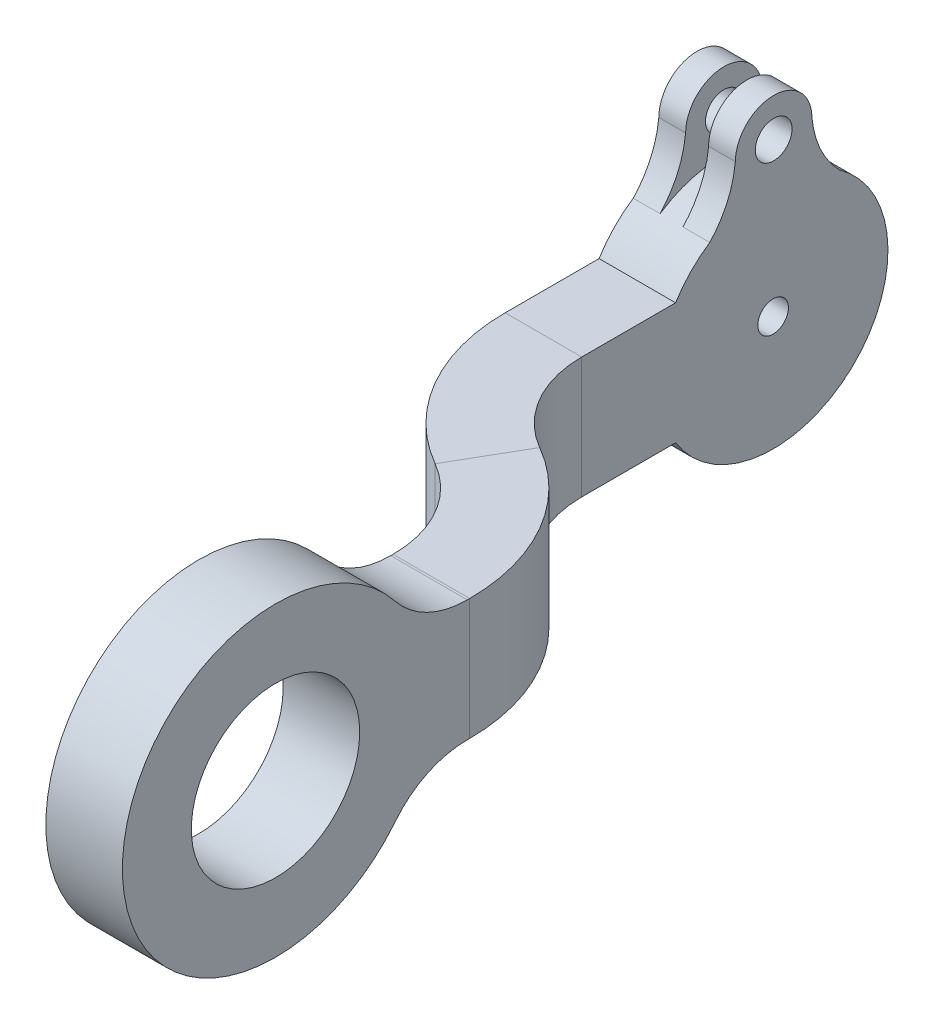
SolidWorks part; units mm, degrees
material "Resina de melamina"
ref_plane "Alzado" through (0, 0, 0) normal (0, 0, 1) x (1, 0, 0)
ref_plane "Planta" through (0, 0, 0) normal (0, 1, 0) x (1, 0, 0)
ref_plane "Vista lateral" through (0, 0, 0) normal (1, 0, 0) x (0, 0, -1)
sketch "Croquis1" plane through (0, 0, 0) normal (0, 1, 0) x (1, 0, 0)
  line L0 (0, 0) -> (0, 60) construction
  line L1 (0, 60) -> (-20, 60) construction
  line L2 (-20, 60) -> (-20, 85) construction
  line L3 (0, 15) -> (-20, 25.359) construction
  line L4 (-20, 85) -> (-20, 60)
  line L5 (0, 25.359) -> (0, 0)
  arc A0 (-20, 60) -> (-10, 42.6795) centre (0, 60) ccw
  arc A1 (0, 25.359) -> (-10, 42.6795) centre (-20, 25.359) ccw
  dimension "D4" = 20
  dimension "D1" = 60
  dimension "D2" = 25
  dimension "D3" = 20
sketch "Croquis2" plane through (0, 0, 0) normal (0, 0, 1) x (1, 0, 0)
  line L1 (5, -7.9175) -> (-5, -7.9175)
  line L2 (5, -7.9175) -> (5, 7.9175)
  line L3 (5, 7.9175) -> (-5, 7.9175)
  line L4 (-5, -7.9175) -> (-5, 7.9175)
  line L5 (5, -7.9175) -> (-5, 7.9175) construction
  line L6 (5, 7.9175) -> (-5, -7.9175) construction
  point P0 (0, 0)
  dimension "D1" = 10
sweep "Barrer1" add profiles "Croquis2" path "Croquis1"
sketch "Croquis4" plane through (-15, 0, 0) normal (1, 0, 0) x (0, 0, -1)
  line L1 (85, -7.9175) -> (85, 7.9175) construction
  circle A0 centre (85, 0) radius 15
  dimension "D2" = 30
extrude "Saliente-Extruir1" add sketch "Croquis4" against normal blind 10
sketch "Croquis5" plane through (5, 0, 0) normal (1, 0, 0) x (0, 0, -1)
  circle A0 centre (0, 0) radius 20
  dimension "D1" = 40
extrude "Saliente-Extruir2" add sketch "Croquis5" against normal blind 10
sketch "Croquis6" plane through (-15, 0, 0) normal (1, 0, 0) x (0, 0, -1)
  line L0 (60, 0) -> (85, 0) construction
  circle A0 centre (85, 0) radius 2
  dimension "D1" = 4
sketch "Croquis7" plane through (5, 0, 0) normal (1, 0, 0) x (0, 0, -1)
  circle A0 centre (0, 0) radius 11
  dimension "D1" = 22
ref_plane "Plano1" through (-15, 0, 0) normal (1, 0, 0) x (0, 0, -1)
sketch "Croquis12" plane through (-15, 0, 0) normal (1, 0, 0) x (0, 0, -1)
  line L0 (85.0685, -0.0274) -> (85.0685, 24.9726) construction
  line L1 (85.0685, 24.9726) -> (85.0685, 19.9726) construction
  line L2 (85.0685, 24.9726) -> (85.0685, 14.9726) construction
  arc A0 (90.0685, 19.9726) -> (80.0685, 19.9726) centre (85.0685, 19.9726) ccw
  arc A1 (94.2885, 11.6439) -> (75.8485, 11.6439) centre (85.0685, -0.0274) ccw
  spline S0 degree 2 poles (80.0685, 19.9726) (79.5667, 15.0283) (75.8485, 11.6439) knots 0 0 0 1 1 1
  spline S1 degree 2 poles (90.0685, 19.9726) (90.5703, 15.0283) (94.2885, 11.6439) knots 0 0 0 1 1 1
  dimension "D1" = 25
  dimension "D2" = 5
extrude "Saliente-Extruir5" add sketch "Croquis12" against normal blind 3.5
ref_plane "Plano2" through (-20, 0, 0) normal (1, 0, 0) x (0, 0, -1)
mirror "Simetría1" about plane through (-20, 0, 0) normal (1, 0, 0) of "Saliente-Extruir5"
sketch "Croquis13" plane through (-15, 0, 0) normal (1, 0, 0) x (0, 0, -1)
  circle A0 centre (85.0685, 19.9726) radius 2.4
  dimension "D1" = 4.8
extrude "Cortar-Extruir1" cut sketch "Croquis13" against normal blind 10
extrude "Cortar-Extruir3" cut sketch "Croquis7" against normal blind 10
fillet "Redondeo2" radius 12 1 edges at (0, 7.9175, -18.3661) type face fillet first side face at (0, 7.9175, -21.8625) second side face at (0, 0, 0.8169)
fillet "Redondeo3" radius 12 1 edges at (0, -7.9175, -18.3661) type face fillet first side face at (0, -7.9175, -21.8625) second side face at (0, -0.1875, 1.4075)
sketch "Croquis14" plane through (-25, 0, 0) normal (-1, 0, 0) x (0, 0, 1)
  circle A0 centre (-85, 0) radius 11.5
  dimension "D1" = 23
extrude "Cortar-Extruir4" cut sketch "Croquis14" against normal blind 5.5
extrude "Cortar-Extruir5" cut sketch "Croquis6" against normal blind 6 contours A0
